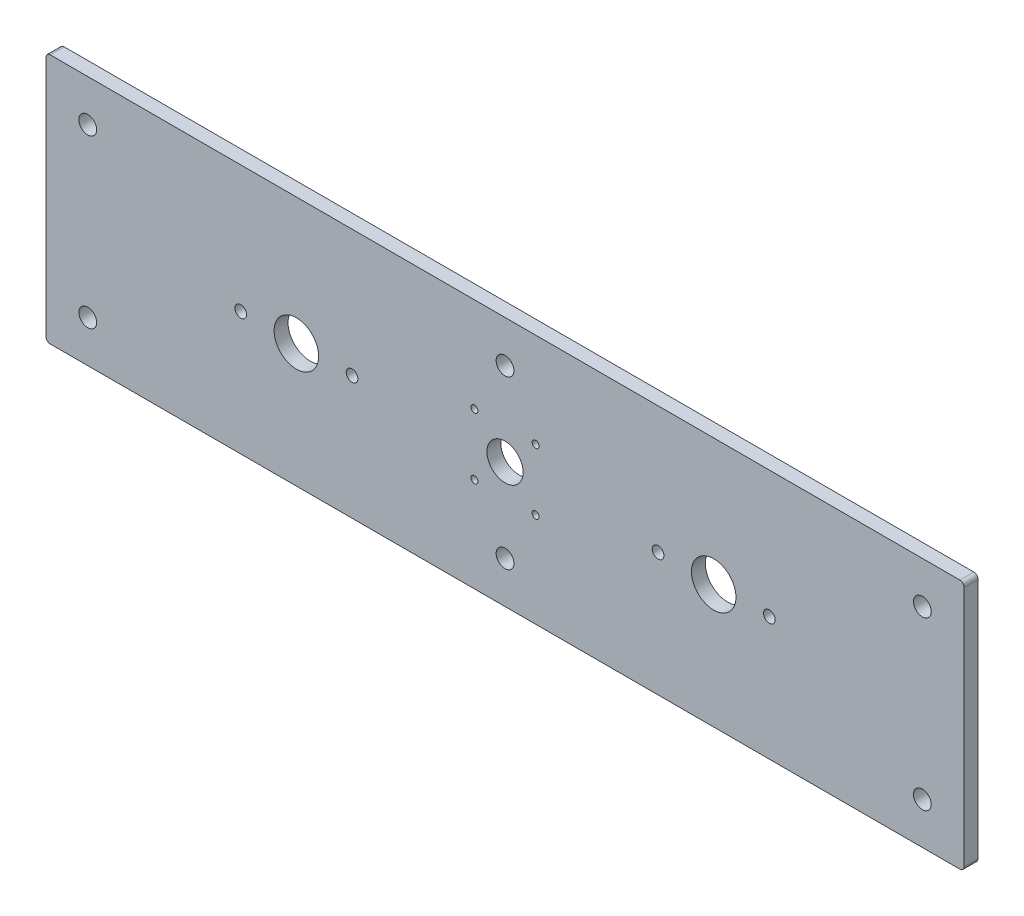
SolidWorks part; units mm, degrees
ref_plane "Front Plane" through (0, 0, 0) normal (0, 0, 1) x (1, 0, 0)
ref_plane "Top Plane" through (0, 0, 0) normal (0, 1, 0) x (1, 0, 0)
ref_plane "Right Plane" through (0, 0, 0) normal (1, 0, 0) x (0, 0, -1)
sketch "Sketch1" plane through (0, 0, 0) normal (0, 0, 1) x (1, 0, 0)
  line L1 (-165, -45) -> (165, -45)
  line L2 (-165, -45) -> (-165, 45)
  line L3 (-165, 45) -> (165, 45)
  line L4 (165, -45) -> (165, 45)
  line L5 (-165, -45) -> (165, 45) construction
  line L6 (-165, 45) -> (165, -45) construction
  point P0 (0, 0)
  dimension "D1" = 330
  dimension "D2" = 90
extrude "Boss-Extrude1" add sketch "Sketch1" along normal mid plane 5
hole_wizard "M6 Clearance Hole1" positions "Sketch6" profile "Sketch5" hole size "M6" standard "ANSI Metric"
sketch "Sketch6" plane through (0, 0, 2.5) normal (0, 0, 1) x (1, 0, 0)
  line L0 (-999.1588, 30) -> (49000.8412, 30) construction
  line L1 (-996.5045, -30) -> (49003.4955, -30) construction
  line L2 (-150, -995.3212) -> (-150, 49004.6788) construction
  line L3 (0, -1000) -> (0, 49000) construction
  line L4 (150, -1006.2702) -> (150, 48993.7298) construction
  line L5 (-165, 45) -> (-165, -45) construction
  line L6 (165, -45) -> (165, 45) construction
  line L7 (165, 45) -> (-165, 45) construction
  line L8 (-165, -45) -> (165, -45) construction
  point P27 (-150, 30)
  point P29 (-150, -30)
  point P31 (0, 30)
  point P33 (0, -30)
  point P35 (150, -30)
  point P37 (150, 30)
  dimension "D1" = 15
  dimension "D2" = 15
  dimension "D3" = 15
  dimension "D4" = 15
sketch "Sketch5" plane through (-150, 30, 2.5) normal (1, 0, 0) x (0, -1, 0)
  line L0 (0, 0) -> (0, 11.9228)
  line L1 (0, 11.9228) -> (3.2, 10)
  line L2 (3.2, 10) -> (3.2, 0)
  line L5 (3.2, 0) -> (0, 0)
  line L10 (0, 11.9228) -> (-3.2, 10) construction
  line L11 (0, -6.35) -> (0, 107.95) construction
  dimension "Hole Dia." = 6.4
  dimension "Hole Depth" = 10
  dimension "Drill Angle" = 118
sketch "Sketch3" plane through (0, 0, 2.5) normal (0, 0, 1) x (1, 0, 0)
  line L0 (-165, -0.6) -> (165, -0.6) construction
  circle A0 centre (-75, -0.6) radius 8
  dimension "D1" = 16
  dimension "D7" = 75
  dimension "D3" = 0.6
extrude "Cut-Extrude2" cut sketch "Sketch3" against normal through all
hole_wizard "M5x0.8 Tapped Hole1" positions "Sketch8" profile "Sketch7" tap size "M5x0.8" standard "ANSI Metric" end condition through all
sketch "Sketch8" plane through (0, 0, 2.5) normal (0, 0, 1) x (1, 0, 0)
  line L0 (-1080, -0.6) -> (48920, -0.6) construction
  circle A0 centre (-75, -0.6) radius 8 construction
  point P6 (-95, -0.6)
  point P8 (-55, -0.6)
  dimension "D1" = 20
  dimension "D2" = 20
sketch "Sketch7" plane through (-95, -0.6, 2.5) normal (1, 0, 0) x (0, -1, 0)
  line L0 (0, 0) -> (0, 5)
  line L1 (0, 5) -> (2.1, 5)
  line L2 (2.1, 5) -> (2.1, 0)
  line L5 (2.1, 0) -> (0, 0)
  line L11 (0, -6.35) -> (0, 107.95) construction
  dimension "Thru Tap Drill Dia." = 4.2
  dimension "Thru Tap Drill Depth" = 5
cosmetic thread "Hole Thread1" parameters "D2"=5
cosmetic thread "Hole Thread2" parameters "D2"=5
mirror "Mirror1" about plane through (0, 0, 0) normal (1, 0, 0) of "M5x0.8 Tapped Hole1", "Cut-Extrude2"
sketch "Sketch4" plane through (0, 0, 2.5) normal (0, 0, 1) x (1, 0, 0)
  circle A0 centre (0, 0) radius 6.5
  dimension "D1" = 13
extrude "Cut-Extrude3" cut sketch "Sketch4" against normal through all
hole_wizard "M3x0.5 Tapped Hole1" positions "Sketch10" profile "Sketch9" tap size "M3x0.5" standard "ANSI Metric" end condition through all
sketch "Sketch10" plane through (0, 0, 2.5) normal (0, 0, 1) x (1, 0, 0)
  line L1 (-11, -11) -> (11, -11) construction
  line L2 (-11, -11) -> (-11, 11) construction
  line L3 (-11, 11) -> (11, 11) construction
  line L4 (11, -11) -> (11, 11) construction
  line L5 (-11, -11) -> (11, 11) construction
  line L6 (-11, 11) -> (11, -11) construction
  point P2 (11, 11)
  point P67 (-11, -11)
  point P68 (-11, 11)
  point P69 (11, -11)
  dimension "D1" = 22
  dimension "D2" = 22
  dimension "D3" = 11
  dimension "D4" = 11
sketch "Sketch9" plane through (11, 11, 2.5) normal (1, 0, 0) x (0, -1, 0)
  line L0 (0, 0) -> (0, 5)
  line L1 (0, 5) -> (1.25, 5)
  line L2 (1.25, 5) -> (1.25, 0)
  line L5 (1.25, 0) -> (0, 0)
  line L11 (0, -6.35) -> (0, 107.95) construction
  dimension "Thru Tap Drill Dia." = 2.5
  dimension "Thru Tap Drill Depth" = 5
cosmetic thread "Hole Thread3" parameters "D2"=3
cosmetic thread "Hole Thread4" parameters "D2"=3
cosmetic thread "Hole Thread5" parameters "D2"=3
cosmetic thread "Hole Thread6" parameters "D2"=3
fillet "Fillet1" radius 1.5 4 edges at (-165, -45, 0) (-165, 45, 0) (165, -45, 0) (165, 45, 0)
